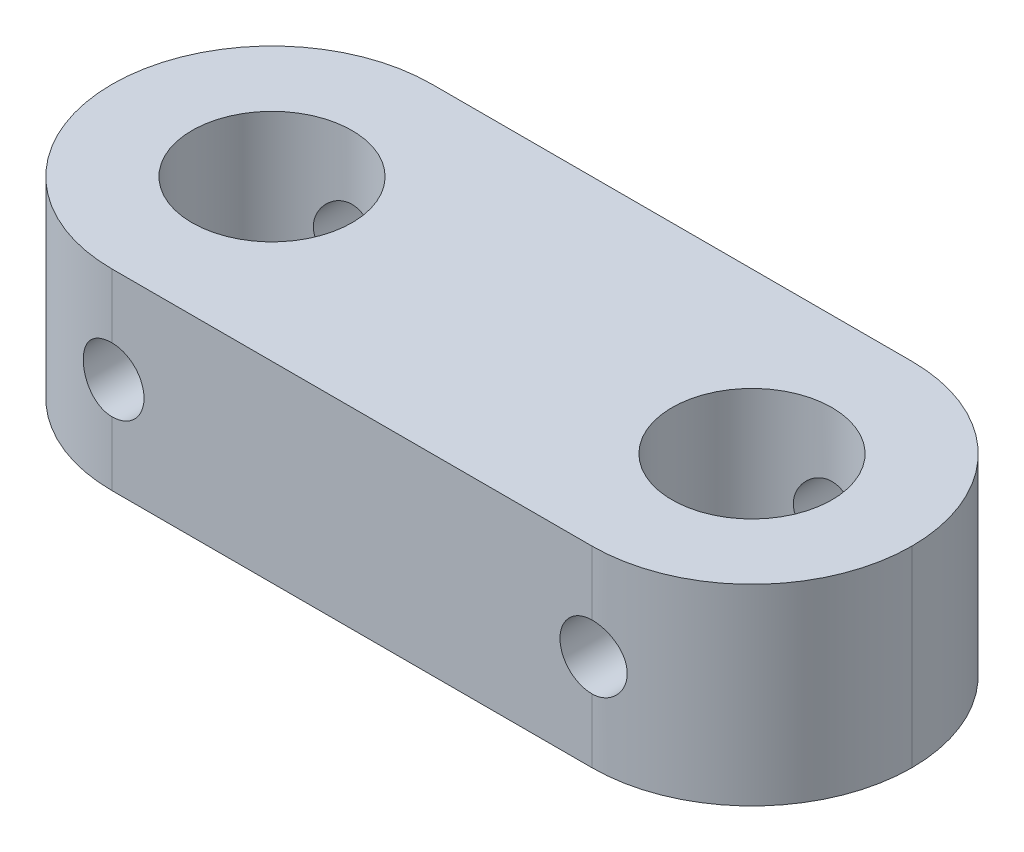
SolidWorks part; units mm, degrees
ref_plane "前视基准面" through (0, 0, 0) normal (0, 0, 1) x (1, 0, 0)
ref_plane "上视基准面" through (0, 0, 0) normal (0, 1, 0) x (1, 0, 0)
ref_plane "右视基准面" through (0, 0, 0) normal (1, 0, 0) x (0, 0, -1)
sketch "草图1" plane through (0, 0, 0) normal (0, 0, 1) x (1, 0, 0)
  line L1 (0, 0) -> (75, 0)
  line L2 (0, 0) -> (0, -18)
  line L3 (0, -18) -> (75, -18)
  line L4 (75, 0) -> (75, -18)
  dimension "D1" = 75
  dimension "D2" = 18
extrude "拉伸1" add sketch "草图1" along normal blind 30
sketch "草图9" plane through (0, 0, 0) normal (0, 1, 0) x (1, 0, 0)
  line L0 (0, -30) -> (0, 0) construction
  circle A0 centre (15, -15) radius 7.5
  dimension "D1" = 15
  dimension "D2" = 15
extrude "切除-拉伸6" cut sketch "草图9" against normal blind 100
fillet "圆角1" radius 15 4 edges at (75, -9, 0) (75, -9, 30) (0, -9, 0) (0, -9, 30)
sketch "草图10" plane through (0, -18, 0) normal (0, -1, 0) x (1, 0, 0)
  circle A0 centre (60, 15) radius 7.5
  dimension "D1" = 15
extrude "切除-拉伸7" cut sketch "草图10" against normal blind 50
sketch "草图11" plane through (0, 0, 0) normal (0, 0, -1) x (-1, 0, 0)
  line L0 (-60, 0) -> (-60, -18) construction
  line L1 (-15, -18) -> (-15, 0) construction
  circle A0 centre (-60, -9) radius 3
  circle A1 centre (-15, -9) radius 3
  dimension "D1" = 6
extrude "切除-拉伸8" cut sketch "草图11" against normal blind 60
